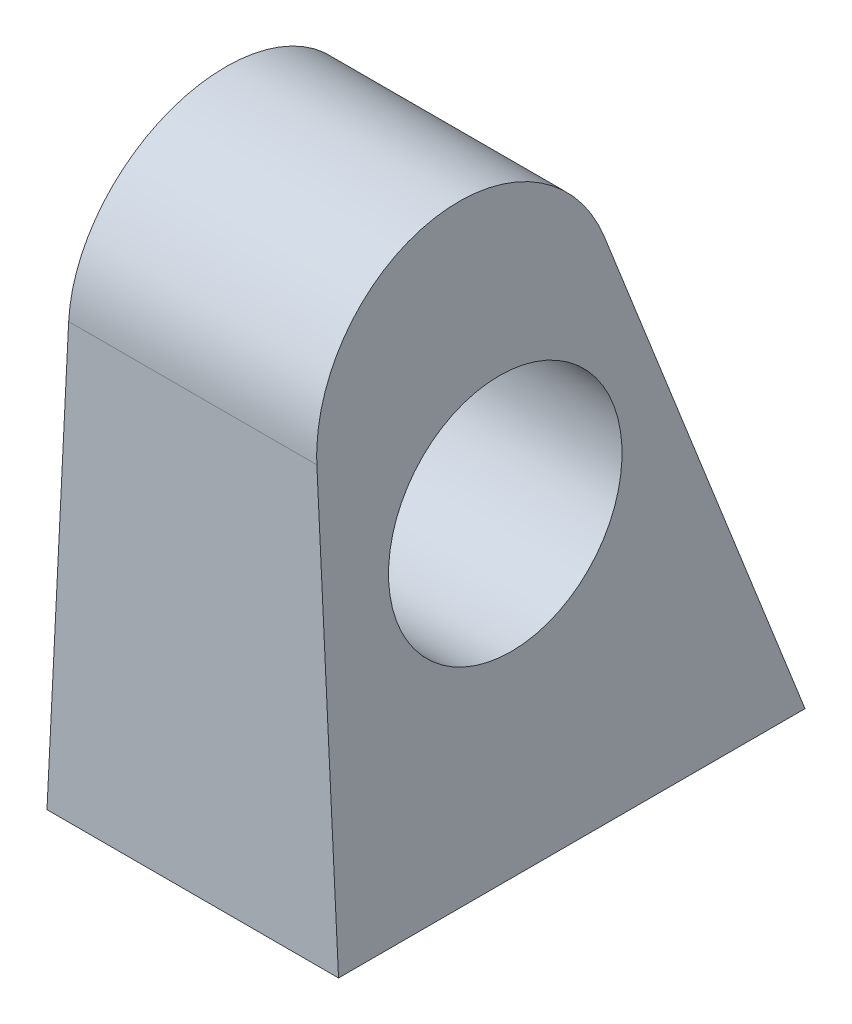
SolidWorks part; units mm, degrees
ref_plane "Front Plane" through (0, 0, 0) normal (0, 0, 1) x (1, 0, 0)
ref_plane "Top Plane" through (0, 0, 0) normal (0, 1, 0) x (1, 0, 0)
ref_plane "Right Plane" through (0, 0, 0) normal (1, 0, 0) x (0, 0, -1)
sketch "Sketch1" plane through (0, 0, 0) normal (1, 0, 0) x (0, 0, -1)
  line L0 (1.547, 13.1962) -> (6.35, 0)
  line L1 (6.35, 0) -> (-6.35, 0)
  line L2 (-6.35, 0) -> (-6.35, 11.8037)
  line L3 (-10.0809, 15.875) -> (13.4038, 15.875) construction
  arc A3 (1.547, 13.1962) -> (-6.35, 11.8037) centre (-2.2787, 11.8037) ccw
  circle A4 centre (-1.3975, 8.2661) radius 3.175
  point P8 (0, 0)
  dimension "D1" = 15.875
  dimension "D3" = 70
  dimension "D4" = 6.35
  dimension "D2" = 12.7
extrude "Boss-Extrude1" add sketch "Sketch1" along normal blind 7.9375
sketch "Sketch2" plane through (0, 0, 6.35) normal (0, 0, 1) x (1, 0, 0)
  line L0 (0, 0) -> (7.9375, 0)
  line L1 (7.9375, 0) -> (7.1437, 15.875)
  line L2 (7.9375, 15.875) -> (0, 15.875) construction
  line L3 (7.1437, 15.875) -> (0.7938, 15.875)
  line L4 (0.7938, 15.875) -> (0, 0)
  point P8 (3.9688, 15.875)
  point P9 (3.9688, 0)
  dimension "D1" = 6.35
extrude "Cut-Extrude1" cut sketch "Sketch2" against normal through all flip side to cut
equation "\"D1@Boss-Extrude1\"=5/16in"
